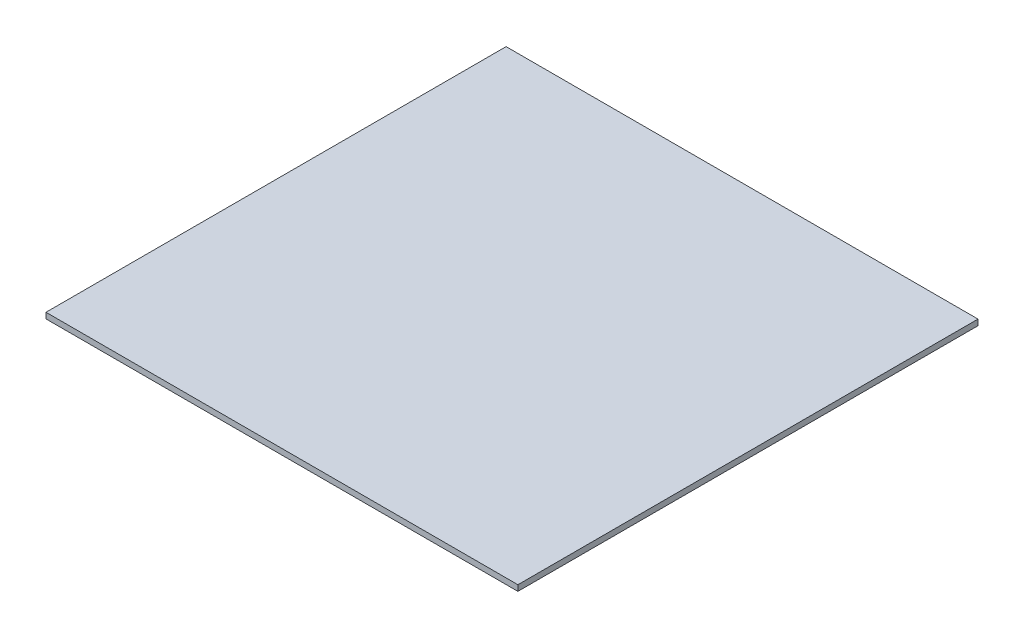
SolidWorks part; units mm, degrees
note: The reader was unsure of these and kept them because the rebuilt part matched: thickness of "Base-Flange2", "Sheet-Metal2".
ref_plane "Front Plane" through (0, 0, 0) normal (0, 0, 1) x (1, 0, 0)
ref_plane "Top Plane" through (0, 0, 0) normal (0, 1, 0) x (1, 0, 0)
ref_plane "Right Plane" through (0, 0, 0) normal (1, 0, 0) x (0, 0, -1)
sketch "Sketch2" plane through (0, 0, 0) normal (0, 1, 0) x (1, 0, 0)
  line L0 (0, 390) -> (0, 0) construction
  line L1 (-200, 0) -> (200, 0)
  line L2 (-200, 0) -> (-200, 390)
  line L3 (-200, 390) -> (200, 390)
  line L4 (200, 0) -> (200, 390)
  line L6 (-160, 35) -> (140, 35) construction
  line L7 (-160, 35) -> (-160, 320) construction
  line L8 (-160, 320) -> (140, 320) construction
  line L9 (140, 35) -> (140, 320) construction
  dimension "D1" = 400
  dimension "D2" = 390
  dimension "D3" = 60
  dimension "80" = 40
  dimension "D4" = 35
  dimension "D5" = 70
base flange "Base-Flange2" sketch "Sketch2" thickness 4.9 reverse thickness direction no parameters "D1"=0.7366
sketch "Bend-Lines3" [suppressed] plane through (0, 0, 0) normal (0, 1, 0) x (1, 0, 0)
sketch "Bounding-Box3" [suppressed] plane through (0, 0, 0) normal (0, 1, 0) x (1, 0, 0)
sheet metal parameters "Sheet-Metal2" thickness 4.9 parameters "D1"=0.7366, "D7"=3
flat pattern "Flat-Pattern2" [suppressed]
sketch "Bend-Lines4" plane through (0, 0, 0) normal (0, 1, 0) x (1, 0, 0)
sketch3d "Bounding-Box4" [suppressed]
  line L0 (200, 390, 0) -> (-200, 390, 0) construction
  line L1 (200, 0, 0) -> (-200, 0, 0) construction
  line L2 (200, 390, 0) -> (200, 0, 0) construction
  line L3 (-200, 390, 0) -> (-200, 0, 0) construction
